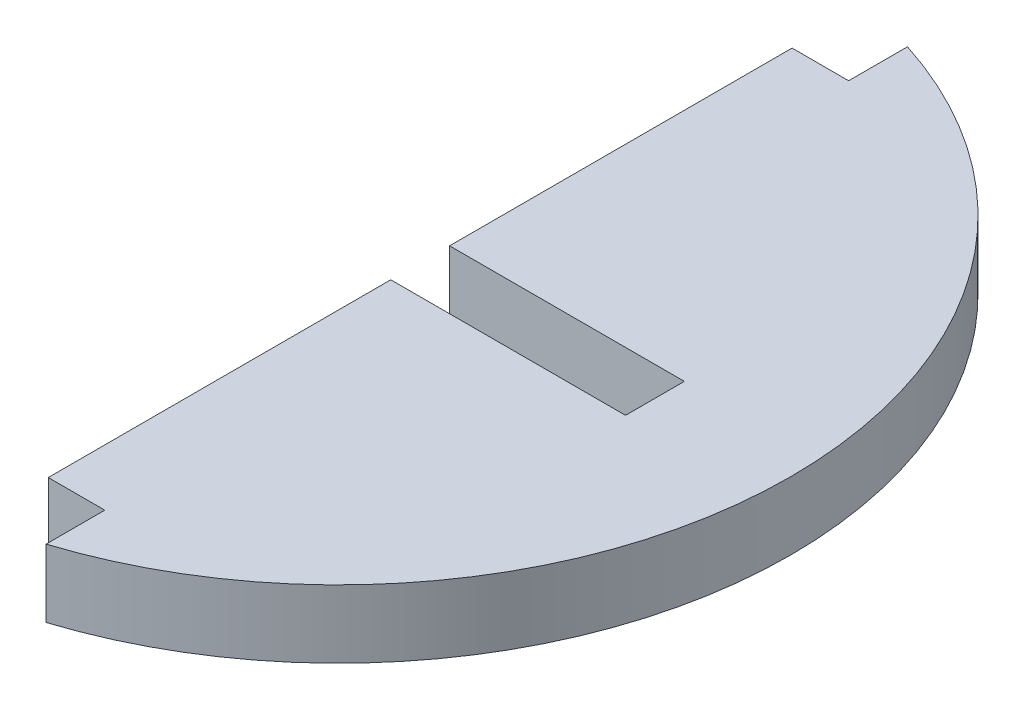
SolidWorks part; units mm, degrees
ref_plane "Front Plane" through (0, 0, 0) normal (0, 0, 1) x (1, 0, 0)
ref_plane "Top Plane" through (0, 0, 0) normal (0, 1, 0) x (1, 0, 0)
ref_plane "Right Plane" through (0, 0, 0) normal (1, 0, 0) x (0, 0, -1)
sketch "Sketch1" plane through (0, 0, 0) normal (0, 1, 0) x (1, 0, 0)
  line L0 (-20, 0) -> (20, 0) construction
  line L1 (-20, 0) -> (20, 0) construction
  line L2 (0, -20) -> (0, 20) construction
  line L4 (3.6213, -1.3) -> (14, -1.3)
  line L5 (14, -1.3) -> (14, 1.3)
  line L6 (14, 1.3) -> (3.6213, 1.3)
  line L9 (6.1213, -19.0402) -> (6.1213, -16.4402)
  line L10 (6.1213, -16.4402) -> (3.6213, -16.4402)
  line L11 (3.6213, -16.4402) -> (3.6213, -1.3)
  line L12 (6.1213, 19.0402) -> (6.1213, 16.4402)
  line L13 (6.1213, 16.4402) -> (3.6213, 16.4402)
  line L14 (3.6213, 16.4402) -> (3.6213, 1.3)
  arc A0 (6.1213, -19.0402) -> (6.1213, 19.0402) centre (0, 0) ccw
  point P4 (0, 0)
  point P5 (14, 0)
  dimension "D1" = 2.6
  dimension "D2" = 2.5
extrude "Boss-Extrude1" add sketch "Sketch1" along normal blind 1.5 and the other way blind 1.5
